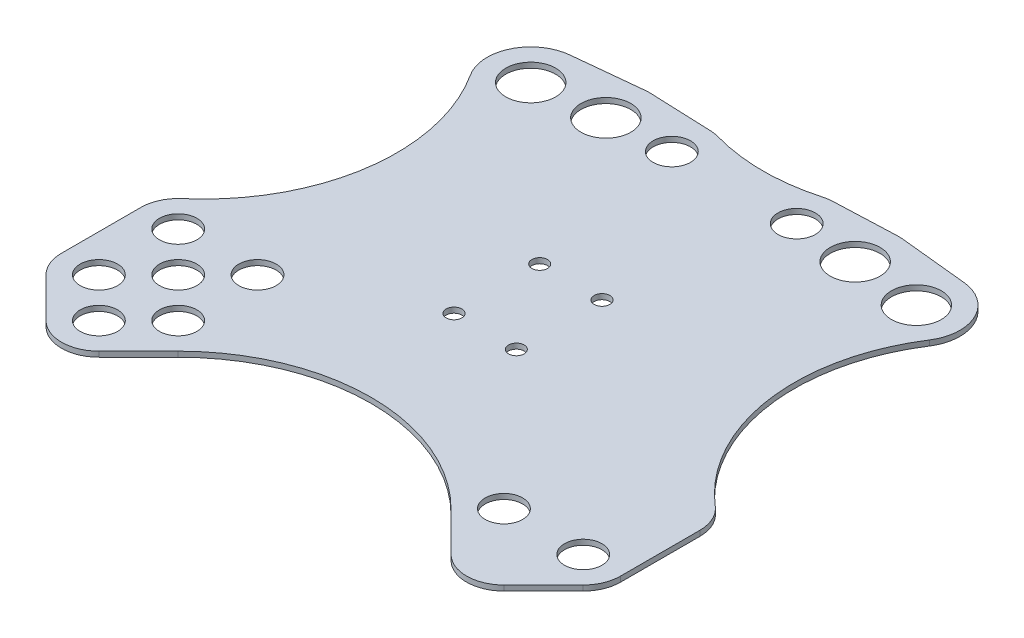
SolidWorks part; units mm, degrees
ref_plane "Front Plane" through (0, 0, 0) normal (0, 0, 1) x (1, 0, 0)
ref_plane "Top Plane" through (0, 0, 0) normal (0, 1, 0) x (1, 0, 0)
ref_plane "Right Plane" through (0, 0, 0) normal (1, 0, 0) x (0, 0, -1)
sketch "Sketch1" plane through (0, 0, 0) normal (0, 1, 0) x (1, 0, 0)
  line L0 (0, 9.3311) -> (0, -58.8842) construction
  line L1 (-10, 13.75) -> (10, 13.75)
  line L2 (-10, 13.75) -> (-10, -13.75)
  line L3 (-10, -13.75) -> (10, -13.75)
  line L4 (10, 13.75) -> (10, -13.75)
  line L5 (-10, 13.75) -> (10, -13.75) construction
  line L6 (-10, -13.75) -> (10, 13.75) construction
  line L7 (-40, 57) -> (-40, 51) construction
  line L8 (-20.0361, 60.201) -> (-20.0361, 54.201) construction
  line L9 (-63.3122, 76.6851) -> (-41.4267, 78.9271)
  line L10 (-60.4587, 48.8309) -> (-38.5733, 51.0729)
  line L11 (-18.1213, 54.3547) -> (-37.7661, 51.1794)
  line L12 (-39.439, 78.9888) -> (-19.5552, 78.1913)
  line L13 (63.3122, 76.6851) -> (41.4267, 78.9271)
  line L14 (39.439, 78.9888) -> (19.5552, 78.1913)
  line L15 (18.1213, 54.3547) -> (37.7661, 51.1794)
  line L16 (60.4587, 48.8309) -> (38.5733, 51.0729)
  line L17 (-65, -72.7279) -> (-52.2721, -60)
  line L18 (-65, -72.7279) -> (-77.7279, -60)
  line L19 (-52.2721, -60) -> (-65, -47.2721)
  line L20 (-77.7279, -60) -> (-65, -47.2721)
  line L21 (-65, -72.7279) -> (-65, -47.2721) construction
  line L22 (-52.2721, -60) -> (-77.7279, -60) construction
  line L23 (-86.2132, -51.5147) -> (-73.4853, -38.7868)
  line L24 (-56.5147, -38.7868) -> (-43.7868, -51.5147)
  line L25 (-43.7868, -68.4853) -> (-56.5147, -81.2132)
  line L26 (-86.2132, -68.4853) -> (-73.4853, -81.2132)
  line L27 (-89.7279, -60) -> (-89.7279, -34.5442)
  line L28 (-40.2721, -60) -> (-40.2721, -34.5442)
  line L29 (-77.7279, -22.5442) -> (-52.2721, -22.5442)
  line L30 (52.2721, -48) -> (77.7279, -48)
  line L31 (52.2721, -72) -> (77.7279, -72)
  line L32 (-77, -47.2721) -> (-71, -47.2721) construction
  circle A0 centre (-10, 13.75) radius 2.5
  circle A1 centre (10, 13.75) radius 2.5
  circle A2 centre (10, -13.75) radius 2.5
  circle A3 centre (-10, -13.75) radius 2.5
  circle A12 centre (0, 0) radius 27.5
  circle A13 centre (0, -433.3974) radius 500
  circle A14 centre (-40, 65) radius 8
  circle A15 centre (-40, 65) radius 14
  circle A16 centre (-61.8855, 62.758) radius 8
  circle A17 centre (-20.0361, 66.201) radius 6
  circle A18 centre (-61.8855, 62.758) radius 14
  circle A19 centre (-20.0361, 66.201) radius 12
  circle A20 centre (20.0361, 66.201) radius 6
  circle A21 centre (40, 65) radius 8
  circle A22 centre (61.8855, 62.758) radius 8
  circle A23 centre (61.8855, 62.758) radius 14
  circle A24 centre (40, 65) radius 14
  circle A25 centre (20.0361, 66.201) radius 12
  circle A26 centre (-65, -47.2721) radius 6
  circle A27 centre (-65, -47.2721) radius 12
  circle A28 centre (-77.7279, -60) radius 6
  circle A29 centre (-77.7279, -60) radius 12
  circle A30 centre (-52.2721, -60) radius 6
  circle A31 centre (-65, -72.7279) radius 6
  circle A32 centre (-65, -72.7279) radius 12
  circle A33 centre (-52.2721, -60) radius 12
  circle A34 centre (-77.7279, -34.5442) radius 6
  circle A35 centre (-52.2721, -34.5442) radius 6
  circle A36 centre (-77.7279, -34.5442) radius 12
  circle A37 centre (-52.2721, -34.5442) radius 12
  circle A38 centre (52.2721, -60) radius 6
  circle A39 centre (52.2721, -60) radius 12
  circle A40 centre (77.7279, -60) radius 12
  circle A41 centre (77.7279, -60) radius 6
  point P0 (0, 0)
  point P13 (-65, -60)
  point P27 (0, 0)
  dimension "D3" = 5
  dimension "D4" = 65
  dimension "D8" = 55
  dimension "D9" = 1000
  dimension "D10" = 16
  dimension "D12" = 6
  dimension "D13" = 12
  dimension "D1" = 20
  dimension "D2" = 27.5
  dimension "D11" = 80
  dimension "D7" = 130
  dimension "D14" = 60
extrude "Boss-Extrude1" add sketch "Sketch1" along normal blind 1.7 contours A3 L3 A2 L4 A1 L1 A0 L2 | A3 L2 A0 L1 A1 L4 A2 L3 | A12 | A19 A15 L11 | A18 L10 A15 | A18 A15 L9 | A19 L12 A15 | A24 A25 L15 | A23 A24 L16 | L13 A24 A23 | L14 A25 A24 | A33 A27 A29 A32 | A33 L24 A27 | A29 A27 L23 | A32 A29 L26 | A33 A32 L25 | A37 L29 A36 A27 | A36 L27 A29 L23 | A37 L24 A33 L28 | L31 A40 L30 A39 | A18 | A16 | A15 | A14 | A19 | A17 | A23 | A22 | A24 | A21 | A25 | A20 | A27 | A26 | A33 | A30 | A29 | A28 | A32 | A31 | A37 | A35 | A36 | A34 | A39 | A38 | A40 | A41 region at (0, 0, 0) region at (-52.2134, 0, -76.2827) region at (-29.3366, 0, -77.2452) region at (-49.672, 0, -51.4753) region at (49.672, 0, -51.4753) region at (-27.9455, 0, -54.1215) region at (52.2134, 0, -76.2827) region at (29.3366, 0, -77.2452) region at (27.9455, 0, -54.1215) region at (-65, 0, 60) region at (-50.9802, 0, 74.0198) region at (-79.0198, 0, 74.0198) region at (-49.6429, 0, 47.6698) region at (-42.8923, 0, 47.2099) region at (-80.3571, 0, 47.6698) region at (-87.1077, 0, 47.2099) region at (-65, 0, 26.0768) region at (65, 0, 60) region at (-26.7222, 0, 0)
sketch "Sketch2" plane through (0, 0, 0) normal (0, -1, 0) x (1, 0, 0)
  line L0 (0, -122.2733) -> (0, 121.7307) construction
  line L1 (-33.6698, 0) -> (48.6645, 0) construction
  line L2 (77.7279, 72) -> (52.2721, 72)
  line L3 (52.2721, 48) -> (77.7279, 48)
  line L4 (-18.1213, -54.3547) -> (-37.7661, -51.1794)
  line L5 (-77.7279, 22.5442) -> (-52.2721, 22.5442)
  line L6 (-89.7279, 60) -> (-89.7279, 34.5442)
  line L7 (-73.4853, 81.2132) -> (-86.2132, 68.4853)
  line L8 (-43.7868, 68.4853) -> (-56.5147, 81.2132)
  line L9 (-40.2721, 34.5442) -> (-40.2721, 60)
  line L10 (-77.7279, 22.5442) -> (-52.2721, 22.5442)
  line L11 (-89.7279, 60) -> (-89.7279, 34.5442)
  line L12 (-73.4853, 81.2132) -> (-86.2132, 68.4853)
  line L13 (-43.7868, 68.4853) -> (-56.5147, 81.2132)
  line L14 (-40.2721, 34.5442) -> (-40.2721, 60)
  line L15 (-39.439, -78.9888) -> (-19.5552, -78.1913)
  line L16 (-63.3122, -76.6851) -> (-41.4267, -78.9271)
  line L17 (-38.5733, -51.0729) -> (-60.4587, -48.8309)
  line L18 (-18.1213, -54.3547) -> (-37.7661, -51.1794)
  line L19 (-39.439, -78.9888) -> (-19.5552, -78.1913)
  line L20 (-63.3122, -76.6851) -> (-41.4267, -78.9271)
  line L21 (-38.5733, -51.0729) -> (-60.4587, -48.8309)
  line L22 (37.7661, -51.1794) -> (18.1213, -54.3547)
  line L23 (60.4587, -48.8309) -> (38.5733, -51.0729)
  line L24 (41.4267, -78.9271) -> (63.3122, -76.6851)
  line L25 (19.5552, -78.1913) -> (39.439, -78.9888)
  line L26 (37.7661, -51.1794) -> (18.1213, -54.3547)
  line L27 (60.4587, -48.8309) -> (38.5733, -51.0729)
  line L28 (41.4267, -78.9271) -> (63.3122, -76.6851)
  line L29 (19.5552, -78.1913) -> (39.439, -78.9888)
  line L30 (77.7279, 72) -> (52.2721, 72)
  line L31 (52.2721, 48) -> (77.7279, 48)
  line L32 (89.7279, 34.5442) -> (89.7279, 60)
  line L34 (89.7279, 60) -> (89.7279, 34.5442)
  line L35 (73.4853, 81.2132) -> (86.2132, 68.4853)
  line L36 (43.7868, 68.4853) -> (56.5147, 81.2132)
  line L37 (40.2721, 34.5442) -> (40.2721, 60)
  line L38 (77.7279, 22.5442) -> (52.2721, 22.5442)
  arc A0 (-89.7279, 34.5442) -> (-75.33, -66.6623) centre (273.1738, 34.5442) ccw
  circle A1 centre (0, 0) radius 27.5
  circle A2 centre (0, 0) radius 27.5
  arc A3 (89.7279, 34.5442) -> (75.33, -66.6623) centre (-273.1738, 34.5442) cw
  arc A4 (-19.5552, -78.1913) -> (-18.1213, -54.3547) centre (-20.0361, -66.201) ccw
  arc A5 (-89.7279, 34.5442) -> (-77.7279, 22.5442) centre (-77.7279, 34.5442) ccw
  arc A6 (-86.2132, 68.4853) -> (-89.7279, 60) centre (-77.7279, 60) ccw
  arc A7 (-56.5147, 81.2132) -> (-73.4853, 81.2132) centre (-65, 72.7279) ccw
  arc A8 (-40.2721, 60) -> (-43.7868, 68.4853) centre (-52.2721, 60) ccw
  arc A9 (-52.2721, 22.5442) -> (-40.2721, 34.5442) centre (-52.2721, 34.5442) ccw
  arc A10 (-89.7279, 34.5442) -> (-77.7279, 22.5442) centre (-77.7279, 34.5442) ccw
  arc A11 (-86.2132, 68.4853) -> (-89.7279, 60) centre (-77.7279, 60) ccw
  arc A12 (-56.5147, 81.2132) -> (-73.4853, 81.2132) centre (-65, 72.7279) ccw
  arc A13 (-40.2721, 60) -> (-43.7868, 68.4853) centre (-52.2721, 60) ccw
  arc A14 (-52.2721, 22.5442) -> (-40.2721, 34.5442) centre (-52.2721, 34.5442) ccw
  arc A15 (-41.4267, -78.9271) -> (-39.439, -78.9888) centre (-40, -65) ccw
  arc A16 (-60.4587, -48.8309) -> (-63.3122, -76.6851) centre (-61.8855, -62.758) ccw
  arc A17 (-37.7661, -51.1794) -> (-38.5733, -51.0729) centre (-40, -65) ccw
  arc A18 (-19.5552, -78.1913) -> (-18.1213, -54.3547) centre (-20.0361, -66.201) ccw
  arc A19 (-41.4267, -78.9271) -> (-39.439, -78.9888) centre (-40, -65) ccw
  arc A20 (-60.4587, -48.8309) -> (-63.3122, -76.6851) centre (-61.8855, -62.758) ccw
  arc A21 (-37.7661, -51.1794) -> (-38.5733, -51.0729) centre (-40, -65) ccw
  arc A22 (18.1213, -54.3547) -> (19.5552, -78.1913) centre (20.0361, -66.201) ccw
  arc A23 (38.5733, -51.0729) -> (37.7661, -51.1794) centre (40, -65) ccw
  arc A24 (63.3122, -76.6851) -> (60.4587, -48.8309) centre (61.8855, -62.758) ccw
  arc A25 (39.439, -78.9888) -> (41.4267, -78.9271) centre (40, -65) ccw
  arc A26 (18.1213, -54.3547) -> (19.5552, -78.1913) centre (20.0361, -66.201) ccw
  arc A27 (38.5733, -51.0729) -> (37.7661, -51.1794) centre (40, -65) ccw
  arc A28 (63.3122, -76.6851) -> (60.4587, -48.8309) centre (61.8855, -62.758) ccw
  arc A29 (39.439, -78.9888) -> (41.4267, -78.9271) centre (40, -65) ccw
  arc A30 (77.7279, 48) -> (77.7279, 72) centre (77.7279, 60) ccw
  arc A31 (52.2721, 72) -> (52.2721, 48) centre (52.2721, 60) ccw
  arc A32 (77.7279, 48) -> (77.7279, 72) centre (77.7279, 60) ccw
  arc A33 (52.2721, 72) -> (52.2721, 48) centre (52.2721, 60) ccw
  circle A34 centre (0, 112.2721) radius 61.9239
  circle A36 centre (-125.7323, -21.6725) radius 61.9239
  arc A37 (86.2132, 68.4853) -> (89.7279, 60) centre (77.7279, 60) cw
  arc A38 (56.5147, 81.2132) -> (73.4853, 81.2132) centre (65, 72.7279) cw
  arc A39 (40.2721, 60) -> (43.7868, 68.4853) centre (52.2721, 60) cw
  arc A40 (52.2721, 22.5442) -> (40.2721, 34.5442) centre (52.2721, 34.5442) cw
  arc A41 (89.7279, 34.5442) -> (77.7279, 22.5442) centre (77.7279, 34.5442) cw
  circle A42 centre (125.7323, -21.6725) radius 61.9239
  circle A43 centre (0, -137.3578) radius 61.9239
  circle M39 centre (0, 0) radius 27.5
  dimension "D1" = 0
  dimension "D2" = 0
  dimension "D3" = 0
  dimension "D4" = 0
  dimension "D5" = 0
extrude "Boss-Extrude2" add sketch "Sketch2" against normal up to surface (1.7 mm away) contours A34 A13 L14 A14 L10 A10 A0 A20 L21 A21 L18 A18 A26 L26 A27 L27 A28 A3 L32 A32 L31 A33 M39 | A41 L32 A32 L31 A33 L37 A40 L38 | A38 L36 A33 L30 A32 L35 region at (65, 0, 76.8996) region at (40.9776, 0, 64.6783) region at (65, 0, 36.5218) up to face at (10, 1.7, 16.25)
